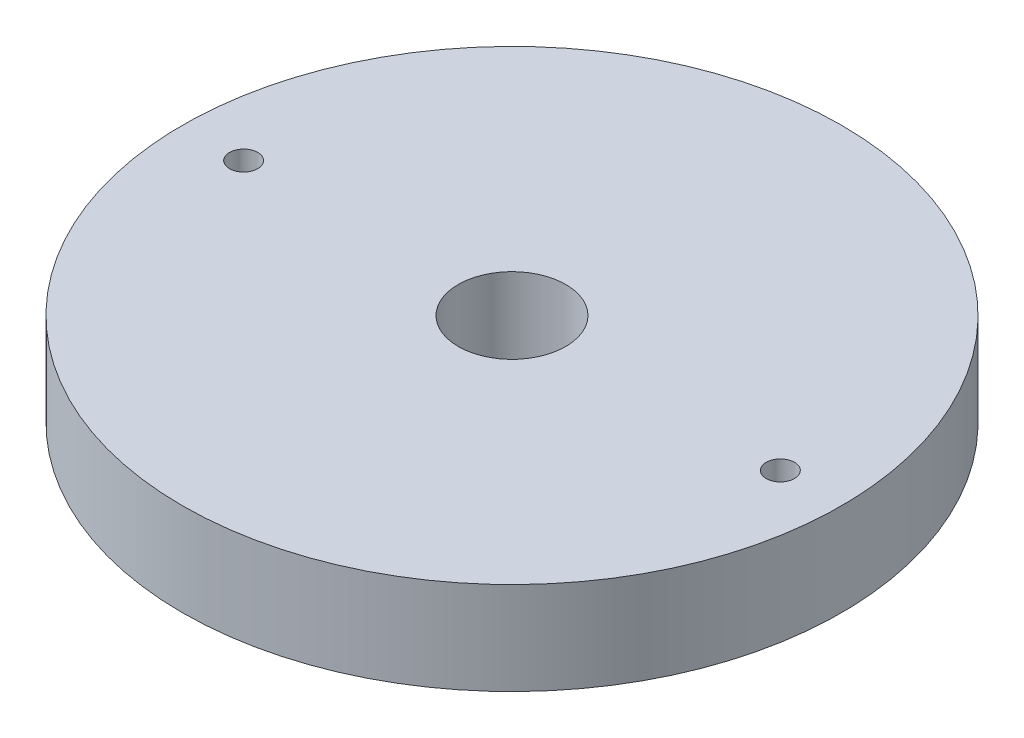
SolidWorks part; units mm, degrees
ref_plane "Front Plane" through (0, 0, 0) normal (0, 0, 1) x (1, 0, 0)
ref_plane "Top Plane" through (0, 0, 0) normal (0, 1, 0) x (1, 0, 0)
ref_plane "Right Plane" through (0, 0, 0) normal (1, 0, 0) x (0, 0, -1)
sketch "Sketch1" plane through (0, 0, 0) normal (0, 1, 0) x (1, 0, 0)
  line L0 (0, 0) -> (-14.478, 0) construction
  line L1 (0, 0) -> (14.478, 0) construction
  circle A0 centre (0, 0) radius 17.78
  circle A1 centre (-14.478, 0) radius 0.762
  circle A2 centre (14.478, 0) radius 0.762
  point P6 (0, 0)
  dimension "D1" = 35.56
  dimension "D2" = 1.524
  dimension "D3" = 1.524
  dimension "D4" = 28.956
extrude "Boss-Extrude1" add sketch "Sketch1" along normal blind 5
sketch "Sketch5" plane through (0, 0, 0) normal (0, -1, 0) x (1, 0, 0)
  circle A0 centre (0, 13.97) radius 2.667
  dimension "D1" = 5.334
  dimension "D2" = 13.97
extrude "Cut-Extrude1" cut sketch "Sketch5" against normal blind 3
hole_wizard "M5 Clearance Hole2" positions "Sketch8" profile "Sketch9" hole size "M5" standard "ANSI Metric" end condition through all
sketch "Sketch8" plane through (0, 5, 0) normal (0, 1, 0) x (1, 0, 0)
  point P0 (0, 0)
sketch "Sketch9" plane through (0, 5, 0) normal (1, 0, 0) x (0, 0, 1)
  line L0 (0, 0) -> (0, 5)
  line L1 (0, 5) -> (2.9, 5)
  line L2 (2.9, 5) -> (2.9, 0)
  line L5 (2.9, 0) -> (0, 0)
  line L11 (0, -6.35) -> (0, 107.95) construction
  dimension "Thru Hole Dia." = 5.8
  dimension "Thru Hole Depth" = 5
equation "\"press fit\"= 0.25mm"
equation "\"servo hole size\"= 0.0472in + \"press fit\""
equation "\"D2@Sketch1\"=\"servo hole size\""
equation "\"D3@Sketch1\"=\"servo hole size\""
equation "\"hole distance\"= 28.9mm"
equation "\"D4@Sketch1\"=\"hole distance\""
equation "\"pin diamiter\"= 5mm"
equation "\"D1@Sketch5\"=\"pin diamiter\"+\"press fit\""
equation "\"middle hole\"= 0.2in"
